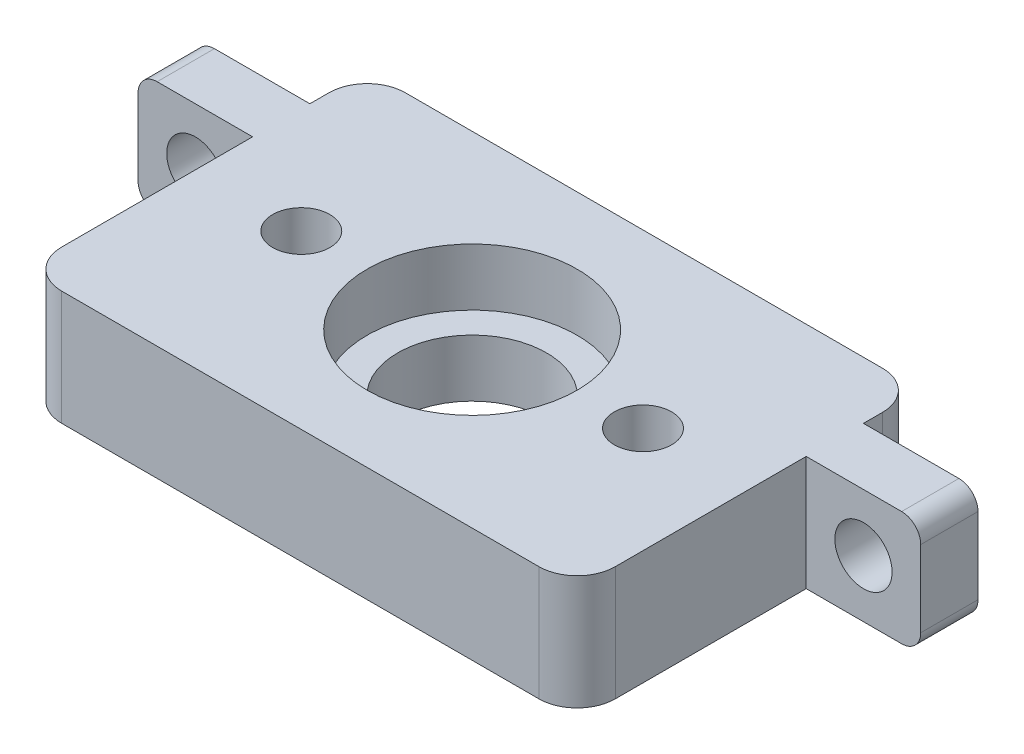
SolidWorks part; units mm, degrees
ref_plane "前视基准面" through (0, 0, 0) normal (0, 0, 1) x (1, 0, 0)
ref_plane "上视基准面" through (0, 0, 0) normal (0, 1, 0) x (1, 0, 0)
ref_plane "右视基准面" through (0, 0, 0) normal (1, 0, 0) x (0, 0, -1)
other "Configuration Table"
sketch "草图1" plane through (0, 0, 0) normal (0, 1, 0) x (1, 0, 0)
  line L0 (29.9, 42.3) -> (0.9, 42.3)
  line L2 (0.9, 33.3) -> (0.9, 51.3)
  line L3 (0.9, 51.3) -> (29.9, 51.3)
  line L4 (29.9, 33.3) -> (29.9, 51.3)
  line L6 (20.9, 42.3) -> (20.9, 51.3)
  line L7 (9.9, 42.3) -> (9.9, 51.3)
  line L8 (0.9, 33.3) -> (29.9, 33.3)
  line L9 (15.4, 51.3) -> (15.4, 33.3) construction
  circle A0 centre (15.4, 42.3) radius 3.9
  circle A1 centre (15.4, 42.3) radius 5.5
  circle A3 centre (6.45, 42.3) radius 1.5
  circle A4 centre (24.35, 42.3) radius 1.5
  point P12 (23.85, 42.3)
  point P13 (27.05, 42.3)
  point P14 (7.95, 42.3)
  point P18 (4.95, 42.3)
  point P19 (24.35, 42.3)
  dimension "D2" = 7.8
  dimension "D3" = 11
  dimension "D9" = 3
  dimension "D12" = 9
  dimension "D6" = 8.95
  dimension "D11" = 3
  dimension "D4" = 29
  dimension "D5" = 8.95
  dimension "D7" = 9
  dimension "D8" = 9
  dimension "D10" = 9
extrude "凸台-拉伸1" add sketch "草图1" along normal blind 6 contours A3 L0 L7 L3 L2 | A1 L6 L3 L7 | A4 L0 L4 L3 L6 | A1 L9 L8 L4 L0 A4 | L3 L9 A1 L6 | L9 A1 L0 A3 L2 L8 region at (23.7234, 0, -37.1692) region at (25.4479, 0, -46.9763) region at (7.0766, 0, -37.1692) region at (18.5337, 0, -48.7989) region at (12.2663, 0, -48.7989) region at (5.3521, 0, -46.9763)
extrude "凸台-拉伸2" add sketch "草图1<6>" along normal blind 3 contours L9 A1 L0 A0 | A1 L9 A0 L0 | A0 L9 A1 L0 | L9 A0 L0 A1 region at (18.421, 0, -39.279) region at (18.421, 0, -45.321) region at (12.379, 0, -39.279) region at (12.379, 0, -45.321)
sketch "草图1<6>" plane through (0, 0, 0) normal (0, 1, 0) x (1, 0, 0) same geometry as "草图1"
ref_plane "基准面1" through (0.9, 0, 0) normal (-1, 0, 0) x (0, 0, 1)
sketch "草图2" plane through (0.9, 0, 0) normal (-1, 0, 0) x (0, 0, 1)
  line L0 (-33.3, 0) -> (-51.3, 0) construction
  line L1 (-33.3, 6) -> (-33.3, 0) construction
  line L2 (-33.3, 6) -> (-51.3, 6) construction
  line L3 (-51.3, 6) -> (-51.3, 0) construction
  line L4 (-33.3, 0) -> (-51.3, 0)
  line L5 (-33.3, 6) -> (-33.3, 0)
  line L6 (-33.3, 6) -> (-51.3, 6)
  line L7 (-51.3, 6) -> (-51.3, 0)
  line L8 (-48.3, 6) -> (-48.3, 0)
  line L9 (-45.3, 6) -> (-45.3, 0)
  dimension "D1" = 6
  dimension "D2" = 3
  dimension "D3" = 3
extrude "凸台-拉伸3" add sketch "草图2" along normal blind 6 contours L9 L6 L8 L4 region at (0.9, 3, -46.8)
ref_plane "基准面5" through (0, 0, -45.3) normal (0, 0, 1) x (1, 0, 0)
sketch "草图4" plane through (0, 0, -45.3) normal (0, 0, 1) x (1, 0, 0)
  line L0 (-5.1, 6) -> (0.9, 6) construction
  line L1 (-5.1, 0) -> (0.9, 0) construction
  line L2 (-5.1, 6) -> (-5.1, 0) construction
  line L3 (0.9, 6) -> (0.9, 0) construction
  line L4 (0.9, 6) -> (0.9, 0)
  line L5 (-5.1, 0) -> (0.9, 0)
  line L6 (-5.1, 6) -> (-5.1, 0)
  line L7 (-5.1, 6) -> (0.9, 6)
  line L8 (-2.1, 6) -> (-2.1, 0) construction
  line L9 (-5.1, 3) -> (0.9, 3) construction
  circle A0 centre (-2.1, 3) radius 1.5
  dimension "D1" = 3
extrude "切除-拉伸1" cut sketch "草图4" against normal blind 6 contours A0 region at (-2.1, 3, -45.3)
ref_plane "基准面6" through (29.9, 0, 0) normal (1, 0, 0) x (0, 0, -1)
sketch "草图5" plane through (29.9, 0, 0) normal (1, 0, 0) x (0, 0, -1)
  line L0 (33.3, 6) -> (33.3, 0) construction
  line L1 (33.3, 0) -> (51.3, 0) construction
  line L2 (51.3, 6) -> (51.3, 0) construction
  line L3 (33.3, 6) -> (51.3, 6) construction
  line L4 (33.3, 6) -> (33.3, 0)
  line L5 (33.3, 0) -> (51.3, 0)
  line L6 (51.3, 6) -> (51.3, 0)
  line L7 (33.3, 6) -> (51.3, 6)
  line L8 (48.3, 6) -> (48.3, 0)
  line L9 (45.3, 6) -> (45.3, 0)
  dimension "D1" = 3
  dimension "D2" = 3
extrude "凸台-拉伸4" add sketch "草图5" along normal blind 6 contours L7 L9 L5 L8 region at (29.9, 3, -46.8)
ref_plane "基准面7" through (0, 0, -48.3) normal (0, 0, -1) x (-1, 0, 0)
sketch "草图7" plane through (0, 0, -48.3) normal (0, 0, -1) x (-1, 0, 0)
  line L0 (-29.9, 6) -> (-29.9, 0) construction
  line L1 (-35.9, 0) -> (-29.9, 0) construction
  line L2 (-35.9, 6) -> (-29.9, 6) construction
  line L3 (-35.9, 6) -> (-35.9, 0) construction
  line L4 (-29.9, 6) -> (-29.9, 0)
  line L5 (-35.9, 0) -> (-29.9, 0)
  line L6 (-35.9, 6) -> (-29.9, 6)
  line L7 (-35.9, 6) -> (-35.9, 0)
  line L8 (-32.9, 6) -> (-32.9, 0) construction
  line L9 (-35.9, 3) -> (-29.9, 3) construction
  circle A0 centre (-32.9, 3) radius 1.5
  dimension "D1" = 3
extrude "切除-拉伸2" cut sketch "草图7" against normal blind 6 contours A0 region at (32.9, 3, -48.3)
fillet "圆角1" radius 2 4 edges at (29.9, 3, -33.3) (0.9, 3, -33.3) (0.9, 3, -51.3) (29.9, 3, -51.3)
fillet "圆角3" radius 1 4 edges at (35.9, 6, -46.8) (35.9, 0, -46.8) (-5.1, 0, -46.8) (-5.1, 6, -46.8)
sketch "草图8" plane through (0, 0, -51.3) normal (0, 0, -1) x (-1, 0, 0)
  circle A0 centre (2.1, 3) radius 1.5 construction
  circle A1 centre (-32.9, 3) radius 1.5 construction
  circle A2 centre (2.1, 3) radius 1.5
  circle A3 centre (-32.9, 3) radius 1.5
